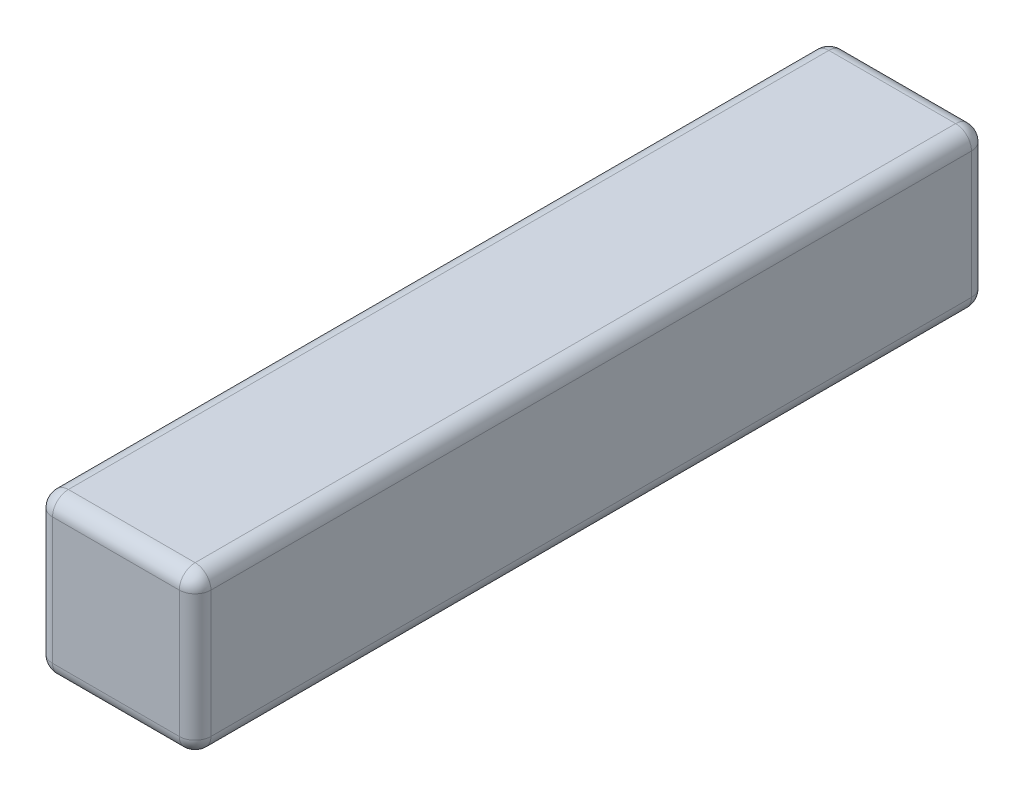
SolidWorks part; units mm, degrees
material "Plain Carbon Steel"
ref_plane "Front Plane" through (0, 0, 0) normal (0, 0, 1) x (1, 0, 0)
ref_plane "Top Plane" through (0, 0, 0) normal (0, 1, 0) x (1, 0, 0)
ref_plane "Right Plane" through (0, 0, 0) normal (1, 0, 0) x (0, 0, -1)
sketch "Sketch1" plane through (0, 0, 0) normal (0, 0, 1) x (1, 0, 0)
  line L1 (-1, -1) -> (1, -1)
  line L2 (-1, -1) -> (-1, 1)
  line L3 (-1, 1) -> (1, 1)
  line L4 (1, -1) -> (1, 1)
  line L5 (-1, -1) -> (1, 1) construction
  line L6 (-1, 1) -> (1, -1) construction
  point P0 (0, 0)
  dimension "D1" = 2
extrude "Boss-Extrude1" add sketch "Sketch1" along normal blind 5 and the other way blind 5
fillet "Fillet1" radius 0.2 12 edges at (0, -1, -5) (-1, 0, -5) (-1, -1, 0) (1, 0, -5) (0, 1, -5) (0, -1, 5) (-1, 0, 5) (-1, 1, 0) (1, -1, 0) (1, 1, 0) (1, 0, 5) (0, 1, 5)
